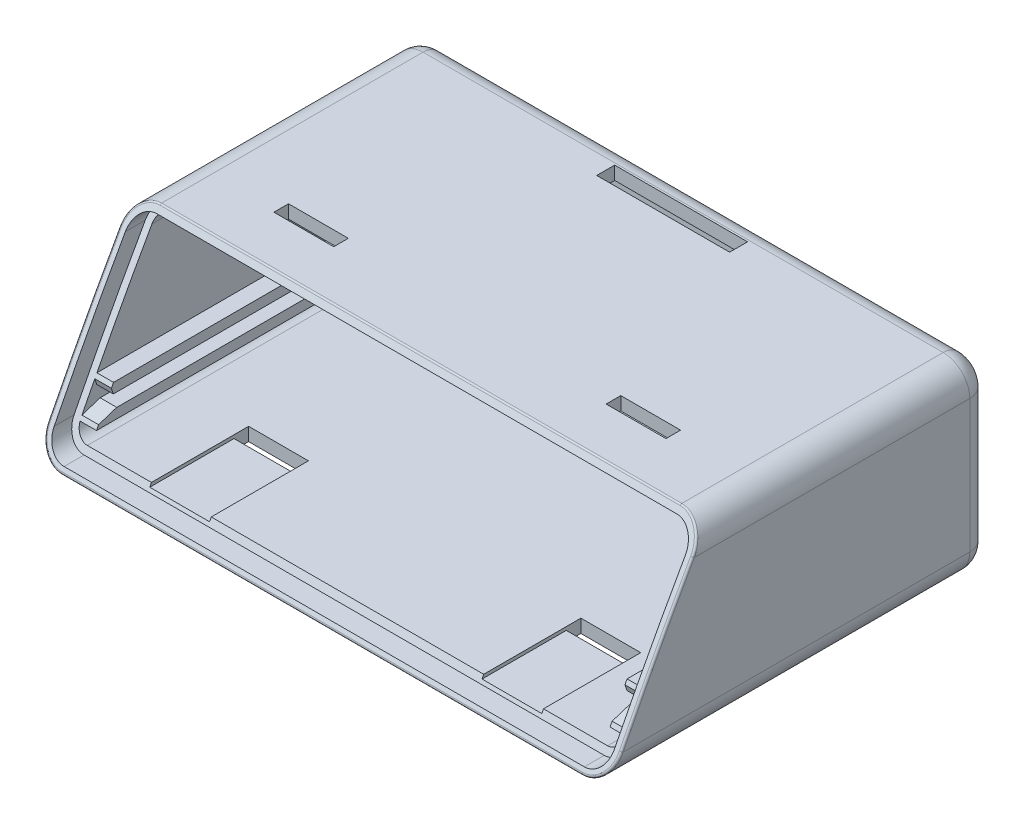
SolidWorks part; units mm, degrees
ref_plane "Front Plane" through (0, 0, 0) normal (0, 0, 1) x (1, 0, 0)
ref_plane "Top Plane" through (0, 0, 0) normal (0, 1, 0) x (1, 0, 0)
ref_plane "Right Plane" through (0, 0, 0) normal (1, 0, 0) x (0, 0, -1)
sketch "Sketch1" plane through (0, 0, 0) normal (0, 1, 0) x (1, 0, 0)
  line L1 (-43.14, -28.75) -> (43.14, -28.75)
  line L2 (-43.14, -28.75) -> (-43.14, 28.75)
  line L3 (-43.14, 28.75) -> (43.14, 28.75)
  line L4 (43.14, -28.75) -> (43.14, 28.75)
  line L5 (-43.14, -28.75) -> (43.14, 28.75) construction
  line L6 (-43.14, 28.75) -> (43.14, -28.75) construction
  point P0 (0, 0)
  dimension "D1" = 57.5
  dimension "D2" = 86.28
extrude "Boss-Extrude1" add sketch "Sketch1" along normal blind 28
fillet "Fillet1" radius 4 4 edges at (43.14, 28, 0) (43.14, 0, 0) (-43.14, 0, 0) (-43.14, 28, 0)
shell "Shell1" thickness 2
sketch "Sketch2" plane through (-43.14, 0, 0) normal (-1, 0, 0) x (0, 0, 1)
  line L0 (-28.75, 28) -> (28.75, 28) construction
  line L1 (13.75, 28) -> (28.75, 28)
  line L2 (28.75, 28) -> (28.75, 0)
  arc A0 (28.75, 0) -> (13.75, 28) centre (-397.2189, -210.1797) ccw
  dimension "D1" = 15
  dimension "D2" = 475
extrude "Cut-Extrude1" cut sketch "Sketch2" against normal through all
sketch "Sketch3" plane through (0, 0, -28.75) normal (0, 0, -1) x (-1, 0, 0)
  line L0 (-7.15, 18.7) -> (7.15, 18.7)
  line L1 (-6.95, 18.5) -> (6.95, 18.5) construction
  line L2 (-6.95, 18.5) -> (-6.95, 2.2) construction
  line L3 (-6.95, 2.2) -> (6.95, 2.2) construction
  line L4 (6.95, 18.5) -> (6.95, 2.2) construction
  line L5 (7.15, 18.7) -> (7.15, 2)
  line L6 (-7.15, 2) -> (7.15, 2)
  line L7 (-7.15, 18.7) -> (-7.15, 2)
  line L8 (27.25, 17.2) -> (38.3, 17.2)
  line L9 (27.45, 17) -> (38.1, 17) construction
  line L10 (27.45, 17) -> (27.45, 3.35) construction
  line L11 (27.45, 3.35) -> (38.1, 3.35) construction
  line L12 (38.1, 17) -> (38.1, 3.35) construction
  line L13 (38.3, 17.2) -> (38.3, 3.15)
  line L14 (27.25, 3.15) -> (38.3, 3.15)
  line L15 (27.25, 17.2) -> (27.25, 3.15)
  dimension "D1" = 0.2
  dimension "D2" = 0.2
extrude "Cut-Extrude2" cut sketch "Sketch3" against normal up to surface (2 mm away) up to face at (0, 14, -26.75)
fillet "Fillet2" radius 3 8 edges at (41.9684, 26.8284, -28.75) (43.14, 14, -28.75) (41.9684, 1.1716, -28.75) (0, 0, -28.75) (-41.9684, 1.1716, -28.75) (-43.14, 14, -28.75) (-41.9684, 26.8284, -28.75) (0, 28, -28.75)
sketch "Sketch4" plane through (0, 0, -26.75) normal (0, 0, 1) x (1, 0, 0)
  line L0 (-7.15, 2) -> (7.15, 2)
  line L1 (-7.15, 1) -> (7.15, 1)
  line L2 (7.15, 1) -> (39.14, 1)
  line L3 (42.14, 4) -> (42.14, 24)
  line L4 (39.14, 27) -> (-39.14, 27)
  line L5 (-42.14, 24) -> (-42.14, 4)
  line L6 (-39.14, 1) -> (-7.15, 1)
  line L8 (-7.15, 18.7) -> (7.15, 18.7)
  line L9 (7.15, 18.7) -> (7.15, 2)
  line L10 (7.15, 2) -> (39.14, 2)
  line L11 (41.14, 4) -> (41.14, 24)
  line L12 (39.14, 26) -> (-39.14, 26)
  line L13 (-41.14, 24) -> (-41.14, 4)
  line L14 (-39.14, 2) -> (-7.15, 2)
  line L15 (-7.15, 2) -> (-7.15, 18.7)
  line L18 (7.15, 2) -> (39.14, 2)
  line L19 (41.14, 4) -> (41.14, 24)
  line L20 (39.14, 26) -> (-39.14, 26)
  line L21 (-41.14, 24) -> (-41.14, 4)
  line L22 (-39.14, 2) -> (-7.15, 2)
  arc A0 (39.14, 1) -> (42.14, 4) centre (39.14, 4) ccw
  arc A1 (42.14, 24) -> (39.14, 27) centre (39.14, 24) ccw
  arc A2 (-39.14, 27) -> (-42.14, 24) centre (-39.14, 24) ccw
  arc A3 (-42.14, 4) -> (-39.14, 1) centre (-39.14, 4) ccw
  arc A4 (39.14, 2) -> (41.14, 4) centre (39.14, 4) ccw
  arc A5 (41.14, 24) -> (39.14, 26) centre (39.14, 24) ccw
  arc A6 (-39.14, 26) -> (-41.14, 24) centre (-39.14, 24) ccw
  arc A7 (-41.14, 4) -> (-39.14, 2) centre (-39.14, 4) ccw
  arc A8 (39.14, 2) -> (41.14, 4) centre (39.14, 4) ccw
  arc A9 (41.14, 24) -> (39.14, 26) centre (39.14, 24) ccw
  arc A10 (-39.14, 26) -> (-41.14, 24) centre (-39.14, 24) ccw
  arc A11 (-41.14, 4) -> (-39.14, 2) centre (-39.14, 4) ccw
  dimension "D1" = 0
  dimension "D2" = 1
extrude "Cut-Extrude3" cut sketch "Sketch4" against normal offset from surface (29.4971 mm away) 3 from offset 80
fillet "Fillet3" radius 0.3 8 edges at (41.7842, 27.0013, 14.3272) (43.14, 14.064, 21.517) (41.4452, 0.7311, 28.3885) (0, 0, 28.75) (-42.0581, 1.2642, 28.1239) (-43.14, 14.064, 21.517) (-41.3892, 27.3077, 14.1504) (0, 28, 13.75)
sketch "Sketch5" plane through (0, 0, -26.75) normal (0, 0, 1) x (1, 0, 0)
  line L0 (41.14, 24) -> (41.14, 4) construction
  line L1 (41.14, 5.25) -> (38.64, 5.25)
  line L2 (41.14, 5.25) -> (41.14, 3.75)
  line L3 (41.14, 3.75) -> (38.64, 3.75)
  line L4 (38.64, 5.25) -> (38.64, 3.75)
  line L5 (34.8894, 7.05) -> (40.64, 7.05) construction
  line L6 (41.14, 7.25) -> (38.64, 7.25)
  line L7 (41.14, 7.25) -> (41.14, 8.75)
  line L8 (41.14, 8.75) -> (38.64, 8.75)
  line L9 (38.64, 7.25) -> (38.64, 8.75)
  line L10 (-40.64, 7.05) -> (40.64, 7.05) construction
  line L11 (40.64, 5.45) -> (34.7752, 5.45) construction
  line L12 (-40.64, 5.45) -> (40.64, 5.45) construction
  line L13 (-41.14, 4) -> (-41.14, 24) construction
  line L14 (-41.14, 8.75) -> (-38.64, 8.75)
  line L15 (-41.14, 8.75) -> (-41.14, 7.25)
  line L16 (-41.14, 7.25) -> (-38.64, 7.25)
  line L17 (-38.64, 8.75) -> (-38.64, 7.25)
  line L19 (-41.14, 5.25) -> (-38.64, 5.25)
  line L20 (-41.14, 5.25) -> (-41.14, 3.75)
  line L21 (-41.14, 3.75) -> (-38.64, 3.75)
  line L22 (-38.64, 5.25) -> (-38.64, 3.75)
  dimension "D1" = 0.2
  dimension "D2" = 0.2
  dimension "D3" = 1.5
  dimension "D4" = 2.5
extrude "Boss-Extrude2" add sketch "Sketch5" along normal up to surface (49.8691 mm away)
sketch "Sketch6" plane through (0, 28, 0) normal (0, 1, 0) x (1, 0, 0)
  line L0 (0, 0) -> (0, 25.75) construction
  line L1 (-28.5, -4.33) -> (-28.5, -6.13) construction
  line L2 (21.5, -4.33) -> (28.5, -4.33) construction
  line L3 (21.5, -4.33) -> (21.5, -6.13) construction
  line L4 (21.5, -6.13) -> (28.5, -6.13) construction
  line L5 (28.5, -4.33) -> (28.5, -6.13) construction
  line L6 (20.5, -4.13) -> (29.5, -4.13)
  line L7 (20.5, -4.13) -> (20.5, -6.33)
  line L8 (20.5, -6.33) -> (29.5, -6.33)
  line L9 (39.14, 25.75) -> (-39.14, 25.75) construction
  line L10 (29.5, -4.13) -> (29.5, -6.33)
  line L11 (-21.5, -6.13) -> (-28.5, -6.13) construction
  line L12 (-21.5, -4.33) -> (-21.5, -6.13) construction
  line L13 (-21.5, -4.33) -> (-28.5, -4.33) construction
  line L14 (-29.5, -4.13) -> (-29.5, -6.33)
  line L15 (-20.5, -6.33) -> (-29.5, -6.33)
  line L16 (-20.5, -4.13) -> (-20.5, -6.33)
  line L17 (-20.5, -4.13) -> (-29.5, -4.13)
  dimension "D1" = 0.2
  dimension "D2" = 0.2
  dimension "D3" = 1
  dimension "D4" = 1
extrude "Cut-Extrude4" cut sketch "Sketch6" against normal up to surface (2 mm away) up to face at (0, 26, -7.4237)
sketch "Sketch9" plane through (0, 0, 0) normal (0, -1, 0) x (1, 0, 0)
  line L0 (0, 0) -> (0, -28.75) construction
  line L1 (-21.5, 12.13) -> (-28.5, 12.13) construction
  line L2 (-21.5, 12.13) -> (-21.5, 10.33) construction
  line L3 (-21.5, 10.33) -> (-28.5, 10.33) construction
  line L4 (-28.5, 12.13) -> (-28.5, 10.33) construction
  line L5 (-20.5, 12.33) -> (-29.5, 12.33)
  line L6 (-20.5, 12.33) -> (-20.5, 10.13)
  line L7 (-20.5, 10.13) -> (-29.5, 10.13)
  line L8 (-29.5, 12.33) -> (-29.5, 10.13)
  line L9 (-39.14, -28.75) -> (39.14, -28.75) construction
  line L10 (28.5, 12.13) -> (28.5, 10.33) construction
  line L11 (21.5, 10.33) -> (28.5, 10.33) construction
  line L12 (21.5, 12.13) -> (21.5, 10.33) construction
  line L13 (21.5, 12.13) -> (28.5, 12.13) construction
  line L14 (29.5, 12.33) -> (29.5, 10.13)
  line L15 (20.5, 10.13) -> (29.5, 10.13)
  line L16 (20.5, 12.33) -> (20.5, 10.13)
  line L17 (20.5, 12.33) -> (29.5, 12.33)
  dimension "D1" = 0.2
  dimension "D2" = 0.2
  dimension "D3" = 1
  dimension "D4" = 1
extrude "Cut-Extrude7" cut sketch "Sketch9" against normal up to surface (2 mm away) up to face at (3.9988, 2, -14.1017)
sketch "Sketch7" plane through (0, 28, 0) normal (0, 1, 0) x (1, 0, 0)
  line L0 (-39.14, 28.75) -> (39.14, 28.75) construction
  line L1 (-10, 25.15) -> (10, 25.15)
  line L2 (-10, 25.15) -> (-10, 22.75)
  line L3 (-10, 22.75) -> (10, 22.75)
  line L4 (10, 25.15) -> (10, 22.75)
  line L5 (0, 0) -> (0, 22.75) construction
  dimension "D1" = 3.6
  dimension "D2" = 2.4
  dimension "D3" = 20
extrude "Cut-Extrude5" cut sketch "Sketch7" against normal up to surface (2 mm away) up to face at (-25, 26, 5.23)
sketch "Sketch8" plane through (0, 0, 6.33) normal (0, 0, -1) x (-1, 0, 0)
  line L0 (-29.5, 26) -> (-20.5, 26) construction
  line L1 (-20.5, 26) -> (-20.5, 28) construction
  line L3 (-29.5, 28) -> (-29.5, 26) construction
  line L4 (20.5, 26) -> (29.5, 26)
  line L5 (29.5, 26) -> (29.5, 28)
  line L6 (29.5, 28) -> (20.5, 28)
  line L7 (20.5, 28) -> (20.5, 26)
  line L8 (20.5, 26) -> (29.5, 26)
  line L9 (29.5, 26) -> (29.5, 26.5)
  line L10 (-20.5, 26.5) -> (-29.5, 26.5)
  line L11 (20.5, 26.5) -> (20.5, 26)
  line L20 (-29.5, 26) -> (-20.5, 26)
  line L21 (-20.5, 26) -> (-20.5, 26.5)
  line L23 (-29.5, 26.5) -> (-29.5, 26)
  line L32 (29.5, 26.5) -> (20.5, 26.5)
  dimension "D2" = 0.5
  dimension "D3" = 0.5
  dimension "D1" = 0
extrude "Cut-Extrude6" cut sketch "Sketch8" against normal through all
sketch "Sketch10" plane through (0, 0, 12.33) normal (0, 0, -1) x (-1, 0, 0)
  line L0 (29.5, 1.5) -> (20.5, 1.5)
  line L1 (-20.5, 1.5) -> (-29.5, 1.5)
  line L4 (29.5, 2) -> (20.5, 2)
  line L5 (20.5, 2) -> (20.5, 0)
  line L6 (20.5, 0) -> (29.5, 0)
  line L7 (29.5, 0) -> (29.5, 2)
  line L8 (29.5, 2) -> (20.5, 2)
  line L9 (20.5, 2) -> (20.5, 1.5)
  line L11 (29.5, 1.5) -> (29.5, 2)
  line L12 (-20.5, 2) -> (-29.5, 2)
  line L13 (-29.5, 2) -> (-29.5, 0)
  line L14 (-29.5, 0) -> (-20.5, 0)
  line L15 (-20.5, 0) -> (-20.5, 2)
  line L16 (-20.5, 2) -> (-29.5, 2)
  line L17 (-29.5, 2) -> (-29.5, 1.5)
  line L19 (-20.5, 1.5) -> (-20.5, 2)
  dimension "D3" = 0.5
  dimension "D1" = 0
  dimension "D2" = 0
extrude "Cut-Extrude8" cut sketch "Sketch10" against normal through all
sketch "Sketch11" plane through (0, 0, -26.75) normal (0, 0, 1) x (1, 0, 0)
  line L0 (7.15, 18.7) -> (7.15, 2) construction
  line L1 (-41.14, 5.25) -> (-38.3, 5.25)
  line L2 (-41.14, 5.25) -> (-41.14, 7.25)
  line L3 (-41.14, 7.25) -> (-38.3, 7.25)
  line L4 (41.14, 5.25) -> (41.14, 7.25)
  line L5 (-7.15, 2) -> (-7.15, 18.7) construction
  line L6 (-27.25, 17.2) -> (-27.25, 3.15) construction
  line L7 (-38.3, 3.15) -> (-38.3, 17.2) construction
  line L8 (7.15, 7.25) -> (7.15, 5.25)
  line L9 (-7.15, 5.25) -> (-7.15, 7.25)
  line L10 (-27.25, 7.25) -> (-27.25, 5.25)
  line L11 (-38.3, 5.25) -> (-38.3, 7.25)
  line L12 (-27.25, 5.25) -> (-7.15, 5.25)
  line L13 (-27.25, 7.25) -> (-7.15, 7.25)
  line L14 (7.15, 7.25) -> (41.14, 7.25)
  line L15 (7.15, 5.25) -> (41.14, 5.25)
extrude "Boss-Extrude3" add sketch "Sketch11" along normal blind 0.5
chamfer "Chamfer1" distance 1 angle 45 4 edges at (39.89, 5.25, 23.1191) (39.89, 7.25, 22.0954) (-39.89, 7.25, 22.0954) (-39.89, 5.25, 23.1191)
sketch "Sketch12" plane through (0, 0, -25.15) normal (0, 0, 1) x (1, 0, 0)
  line L4 (10, 26) -> (10, 28)
  line L5 (10, 28) -> (-10, 28)
  line L6 (-10, 28) -> (-10, 26)
  line L7 (-10, 26) -> (10, 26)
  line L8 (10, 26) -> (10, 28)
  line L9 (10, 28) -> (-10, 28)
  line L10 (-10, 28) -> (-10, 26)
  line L11 (-10, 26) -> (10, 26)
  dimension "D1" = 0
extrude "Cut-Extrude9" cut sketch "Sketch12" against normal blind 0.3
